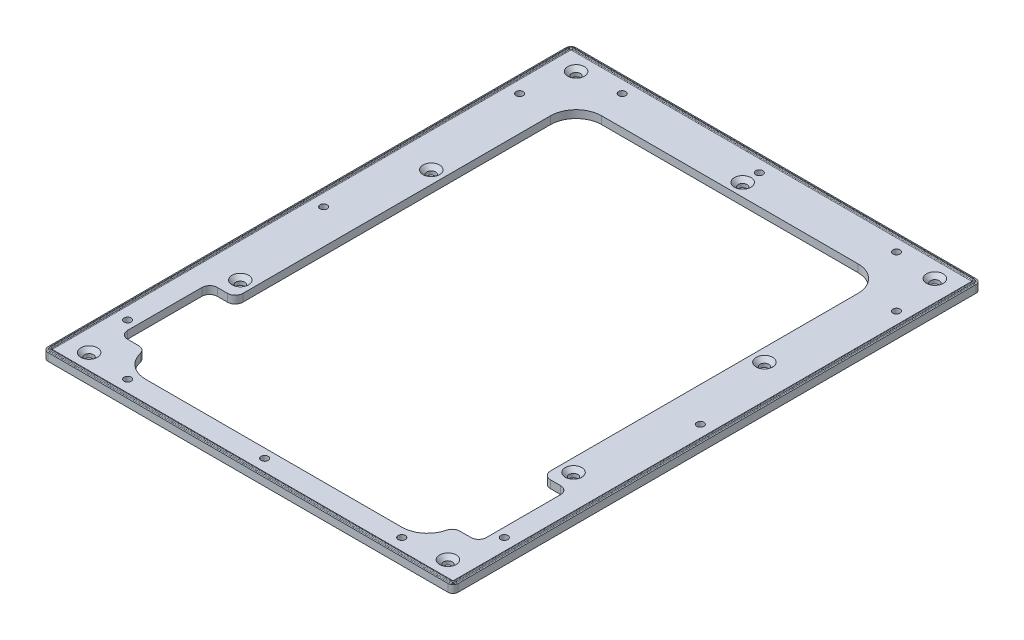
SolidWorks part; units mm, degrees
ref_plane "Front Plane" through (0, 0, 0) normal (0, 0, 1) x (1, 0, 0)
ref_plane "Top Plane" through (0, 0, 0) normal (0, 1, 0) x (1, 0, 0)
ref_plane "Right Plane" through (0, 0, 0) normal (1, 0, 0) x (0, 0, -1)
sketch "Sketch1" plane through (0, 0, 0) normal (0, 1, 0) x (1, 0, 0)
  line L0 (160, -203) -> (160, -3) construction
  line L1 (2, 0) -> (158, 0)
  line L2 (0, -2) -> (0, -204)
  line L3 (2, -206) -> (158, -206)
  line L4 (160, -2) -> (160, -204)
  line L5 (2, -206) -> (158, -206) construction
  arc A0 (0, -204) -> (2, -206) centre (2, -204) ccw
  arc A1 (158, -206) -> (160, -204) centre (158, -204) ccw
  arc A2 (158, 0) -> (160, -2) centre (158, -2) cw
  arc A3 (2, 0) -> (0, -2) centre (2, -2) ccw
  point P13 (160, -206)
  point P16 (160, 0)
  point P19 (0, 0)
  dimension "D3" = 2
  dimension "D1" = 160
  dimension "D2" = 206
extrude "Boss-Extrude1" add sketch "Sketch1" along normal blind 3
sketch "Sketch12" plane through (0, 3, 0) normal (0, 1, 0) x (1, 0, 0)
  circle A0 centre (80, -13) radius 3 construction
  circle A1 centre (10, -8) radius 1.6 construction
  circle A2 centre (15, -69.5) radius 3 construction
  circle A3 centre (15, -144) radius 3 construction
  circle A4 centre (10, -198) radius 1.6 construction
  circle A5 centre (150, -198) radius 2.1 construction
  circle A6 centre (145, -144) radius 3 construction
  circle A7 centre (145, -69.5) radius 3 construction
  circle A8 centre (150, -8) radius 1.6 construction
  circle A9 centre (80, -13) radius 3
  circle A10 centre (10, -8) radius 1.6
  circle A11 centre (15, -69.5) radius 3
  circle A12 centre (15, -144) radius 3
  circle A13 centre (10, -198) radius 1.6
  circle A14 centre (150, -198) radius 2.1
  circle A15 centre (145, -144) radius 3
  circle A16 centre (145, -69.5) radius 3
  circle A17 centre (150, -8) radius 1.6
hole_wizard "CSK for M3 Flat Head Machine Screw1" positions "3DSketch1" profile "Sketch13" countersink size "M3" standard "ANSI Metric" end condition through all
sketch3d "3DSketch1"
  point P0 (10, 3, 8)
  point P3 (80, 3, 13)
  point P6 (150, 3, 8)
  point P9 (145, 3, 69.5)
  point P12 (15, 3, 69.5)
  point P15 (15, 3, 144)
  point P18 (10, 3, 198)
  point P21 (150, 3, 198)
  point P24 (145, 3, 144)
sketch "Sketch13" plane through (10, 3, 8) normal (1, 0, 0) x (0, 0, 1)
  line L0 (0, 0) -> (0, 3)
  line L1 (0, 3) -> (1.7, 3)
  line L2 (1.7, 3) -> (1.7, 1.55)
  line L3 (1.7, 1.55) -> (3.25, 0)
  line L5 (3.25, 0) -> (0, 0)
  line L6 (-1.7, 1.55) -> (-3.25, 0) construction
  line L11 (0, -6.35) -> (0, 107.95) construction
  dimension "Thru Hole Dia." = 3.4
  dimension "Thru Hole Depth" = 3
  dimension "Near C'Sink Dia." = 6.5
  dimension "Near C'Sink Angle" = 90
sketch "Sketch14" plane through (0, 3, 0) normal (0, 1, 0) x (1, 0, 0)
  line L0 (2, -206) -> (158, -206) construction
  line L1 (30, -18) -> (130, -18)
  line L2 (20, -28) -> (20, -186)
  line L3 (30, -196) -> (130, -196)
  line L4 (140, -28) -> (140, -186)
  circle A0 centre (80, -13) radius 3.25 construction
  circle A1 centre (145, -69.5) radius 3.25 construction
  circle A2 centre (15, -69.5) radius 3.25 construction
  arc A3 (20, -186) -> (30, -196) centre (30, -186) ccw
  arc A4 (130, -196) -> (140, -186) centre (130, -186) ccw
  arc A5 (130, -18) -> (140, -28) centre (130, -28) cw
  arc A6 (30, -18) -> (20, -28) centre (30, -28) ccw
  dimension "D1" = 5
  dimension "D2" = 5
  dimension "D3" = 5
  dimension "D5" = 10
  dimension "D4" = 10
extrude "Cut-Extrude8" cut sketch "Sketch14" against normal through all
sketch "Sketch15" plane through (0, 3, 0) normal (0, 1, 0) x (1, 0, 0)
  line L0 (20, -28) -> (20, -186) construction
  line L1 (20, -151) -> (10, -151)
  line L2 (20, -151) -> (20, -186)
  line L3 (20, -186) -> (10, -186)
  line L4 (10, -151) -> (10, -186)
  line L5 (140, -186) -> (140, -28) construction
  line L6 (140, -151) -> (150, -151)
  line L7 (140, -151) -> (140, -186)
  line L8 (140, -186) -> (150, -186)
  line L9 (150, -151) -> (150, -186)
  dimension "D1" = 35
  dimension "D2" = 10
extrude "Cut-Extrude9" cut sketch "Sketch15" against normal through all
fillet "Fillet5" radius 3 8 edges at (150, 1.5, 186) (140, 1.5, 151) (150, 1.5, 151) (10, 1.5, 186) (20, 1.5, 186) (10, 1.5, 151) (20, 1.5, 151) (140, 1.5, 186)
ref_plane "Plane3" through (0, 0, 103) normal (0, 0, -1) x (-1, 0, 0)
ref_plane "Plane4" through (80, 0, 0) normal (-1, 0, 0) x (0, 0, 1)
ref_axis "Axis1" through (80, -0.15, 103) along (0, 1, 0)
sketch "Sketch18" plane through (0, 3, 0) normal (0, 1, 0) x (1, 0, 0)
  line L8 (2, -205.25) -> (158, -205.25)
  line L9 (159.25, -204) -> (159.25, -2)
  line L10 (158, -0.75) -> (2, -0.75)
  line L11 (0.75, -2) -> (0.75, -204)
  line L12 (2, -205.25) -> (158, -205.25)
  line L13 (159.25, -204) -> (159.25, -2)
  line L14 (158, -0.75) -> (2, -0.75)
  line L15 (0.75, -2) -> (0.75, -204)
  line L20 (2, -204.5) -> (158, -204.5)
  line L21 (158.5, -204) -> (158.5, -2)
  line L22 (158, -1.5) -> (2, -1.5)
  line L23 (1.5, -2) -> (1.5, -204)
  line L24 (2, -204.5) -> (158, -204.5)
  line L25 (158.5, -204) -> (158.5, -2)
  line L26 (158, -1.5) -> (2, -1.5)
  line L27 (1.5, -2) -> (1.5, -204)
  arc A8 (0.75, -204) -> (2, -205.25) centre (2, -204) ccw
  arc A9 (158, -205.25) -> (159.25, -204) centre (158, -204) ccw
  arc A10 (159.25, -2) -> (158, -0.75) centre (158, -2) ccw
  arc A11 (2, -0.75) -> (0.75, -2) centre (2, -2) ccw
  arc A12 (0.75, -204) -> (2, -205.25) centre (2, -204) ccw
  arc A13 (158, -205.25) -> (159.25, -204) centre (158, -204) ccw
  arc A14 (159.25, -2) -> (158, -0.75) centre (158, -2) ccw
  arc A15 (2, -0.75) -> (0.75, -2) centre (2, -2) ccw
  arc A20 (1.5, -204) -> (2, -204.5) centre (2, -204) ccw
  arc A21 (158, -204.5) -> (158.5, -204) centre (158, -204) ccw
  arc A22 (158.5, -2) -> (158, -1.5) centre (158, -2) ccw
  arc A23 (2, -1.5) -> (1.5, -2) centre (2, -2) ccw
  arc A24 (1.5, -204) -> (2, -204.5) centre (2, -204) ccw
  arc A25 (158, -204.5) -> (158.5, -204) centre (158, -204) ccw
  arc A26 (158.5, -2) -> (158, -1.5) centre (158, -2) ccw
  arc A27 (2, -1.5) -> (1.5, -2) centre (2, -2) ccw
  dimension "D1" = 0.75
  dimension "D2" = 1.5
extrude "Boss-Extrude2" add sketch "Sketch18" along normal blind 0.5
fillet "Fillet6" radius 0.25 32 edges at (1.1161, 3, 1.1161) (80, 3, 0.75) (158.8839, 3, 1.1161) (159.25, 3, 103) (158.8839, 3, 204.8839) (80, 3, 205.25) (1.1161, 3, 204.8839) (158.3536, 3, 1.6464) (158.5, 3, 103) (158.3536, 3, 204.3536) (80, 3, 204.5) (1.6464, 3, 204.3536) (1.5, 3, 103) (1.6464, 3, 1.6464) (80, 3.5, 1.5) (158.3536, 3.5, 1.6464) (158.5, 3.5, 103) (158.3536, 3.5, 204.3536) (80, 3.5, 204.5) (1.6464, 3.5, 204.3536) (1.5, 3.5, 103) (80, 3.5, 0.75) (158.8839, 3.5, 1.1161) (159.25, 3.5, 103) (158.8839, 3.5, 204.8839) (80, 3.5, 205.25) (1.1161, 3.5, 204.8839) (0.75, 3.5, 103) (0.75, 3, 103) (80, 3, 1.5) (1.6464, 3.5, 1.6464) (1.1161, 3.5, 1.1161)
hole_wizard "Ø3.0mm Dowel Hole1" positions "3DSketch3" profile "Sketch21" hole size "Ø3.0" standard "ANSI Metric" end condition through all
sketch3d "3DSketch3"
  line L0 (133.5, 8.5, 6.5) -> (133.5, 3, 6.5) construction
  line L1 (80, 8.5, 6.5) -> (80, 3, 6.5) construction
  line L2 (26.5, 8.5, 6.5) -> (26.5, 3, 6.5) construction
  line L3 (6.5, 8.5, 26.5) -> (6.5, 3, 26.5) construction
  line L4 (6.5, 8.5, 103) -> (6.5, 3, 103) construction
  line L5 (6.5, 8.5, 179.5) -> (6.5, 3, 179.5) construction
  line L6 (26.5, 8.5, 199.5) -> (26.5, 3, 199.5) construction
  line L7 (80, 8.5, 199.5) -> (80, 3, 199.5) construction
  line L8 (133.5, 8.5, 199.5) -> (133.5, 3, 199.5) construction
  line L9 (153.5, 8.5, 179.5) -> (153.5, 3, 179.5) construction
  line L10 (153.5, 8.5, 103) -> (153.5, 3, 103) construction
  line L11 (153.5, 8.5, 26.5) -> (153.5, 3, 26.5) construction
  point P0 (133.5, 3, 6.5)
  point P4 (80, 8.5, 6.5)
  point P8 (26.5, 3, 6.5)
  point P12 (6.5, 8.5, 26.5)
  point P16 (6.5, 8.5, 103)
  point P20 (6.5, 8.5, 179.5)
  point P24 (26.5, 3, 199.5)
  point P28 (80, 8.5, 199.5)
  point P32 (133.5, 3, 199.5)
  point P36 (153.5, 8.5, 179.5)
  point P40 (153.5, 8.5, 103)
  point P44 (153.5, 3, 26.5)
  point P50 (133.5, 8.5, 6.5)
  point P52 (153.5, 8.5, 26.5)
  point P54 (26.5, 8.5, 6.5)
  point P56 (26.5, 8.5, 199.5)
  point P58 (133.5, 8.5, 199.5)
sketch "Sketch21" plane through (133.5, 3, 6.5) normal (1, 0, 0) x (0, 0, -1)
  line L0 (0, 0) -> (0, 0.5)
  line L1 (0, 0.5) -> (1.4, 0.5)
  line L2 (1.4, 0.5) -> (1.4, 0)
  line L5 (1.4, 0) -> (0, 0)
  line L11 (0, -6.35) -> (0, 107.95) construction
  dimension "Thru Hole Dia." = 2.8
  dimension "Thru Hole Depth" = 0.5
